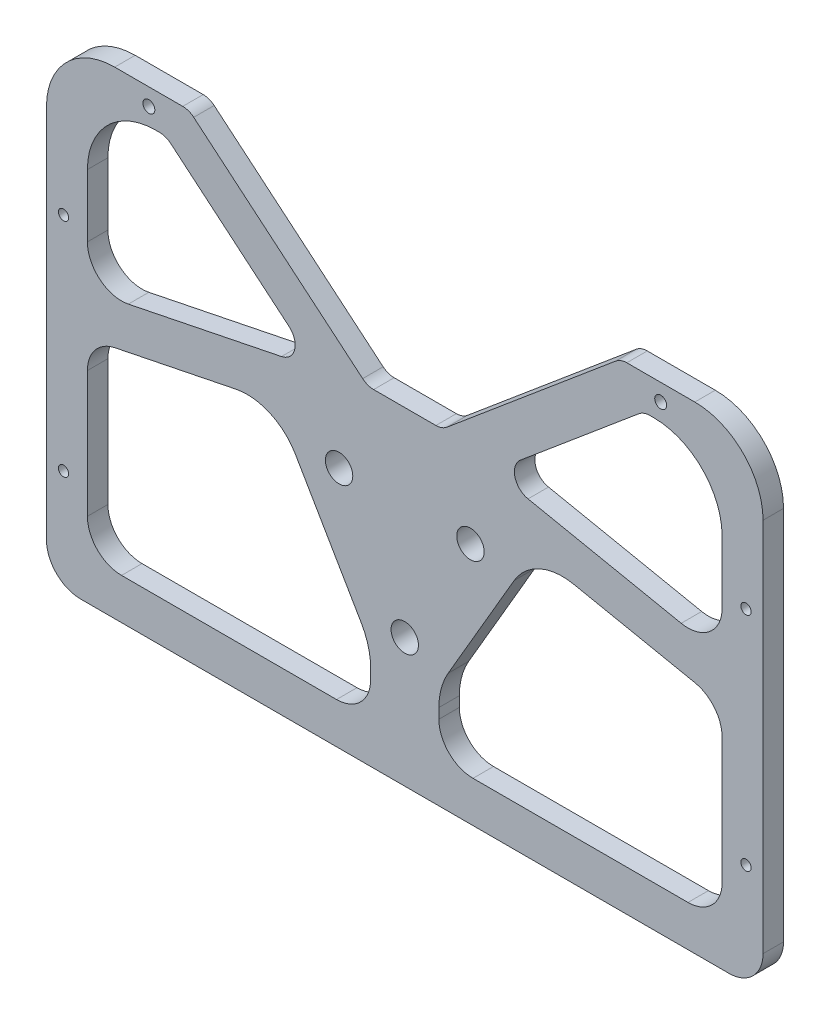
SolidWorks part; units mm, degrees
ref_plane "前基準面" through (0, 0, 0) normal (0, 0, 1) x (1, 0, 0)
ref_plane "上基準面" through (0, 0, 0) normal (0, 1, 0) x (1, 0, 0)
ref_plane "右基準面" through (0, 0, 0) normal (1, 0, 0) x (0, 0, -1)
sketch "Sketch1" plane through (0, 0, 0) normal (0, 0, 1) x (1, 0, 0)
  line L0 (0, 83.5398) -> (0, -125.3098) construction
  line L2 (-95, -60) -> (95, -60)
  line L3 (-105, -50) -> (-105, 60)
  line L5 (105, -50) -> (105, 60)
  line L6 (-105, -60) -> (105, 60) construction
  line L7 (-105, 60) -> (105, -60) construction
  line L8 (93, -1.0046) -> (93, -38)
  line L9 (-83, -48) -> (-20, -48)
  line L10 (-93, -38) -> (-93, -1.0046)
  line L11 (-93, 48) -> (93, 48) construction
  line L12 (93, -48) -> (93, 48) construction
  line L13 (-93, -48) -> (93, -48) construction
  line L14 (-93, -48) -> (-93, 48) construction
  line L15 (-105, 60) -> (105, 60) construction
  line L16 (-105, -60) -> (-105, 60) construction
  line L17 (-105, -60) -> (105, -60) construction
  line L18 (105, -60) -> (105, 60) construction
  line L19 (0, 0) -> (-61.5237, 35.5207) construction
  line L20 (84.9937, 8.7946) -> (49.4486, 16.0264)
  line L21 (-93, 31.651) -> (-93, 50)
  line L22 (-66.8269, 30) -> (70.1999, 30) construction
  line L23 (-84.9937, 8.7946) -> (-49.4486, 16.0264)
  line L24 (-32.0562, 8.2322) -> (-12.7184, -24.9642)
  line L25 (32.0562, 8.2322) -> (12.7184, -24.9642)
  line L26 (20, -48) -> (83, -48)
  line L27 (93, 31.651) -> (93, 50)
  line L28 (-10, -38) -> (-10, -35.0313)
  line L29 (-100, 73.1057) -> (-100, -98.0123) construction
  line L30 (10, -38) -> (10, -35.0313)
  line L31 (100, 71.0716) -> (100, -107.1657) construction
  line L32 (-81.0063, 21.8517) -> (-42.9297, 29.5985)
  line L33 (81.0063, 21.8517) -> (42.9297, 29.5985)
  line L34 (-38.9423, 30) -> (38.9423, 30)
  line L35 (-85, 80) -> (85, 80)
  line L37 (-73, 70) -> (73, 70)
  arc A0 (-105, 60) -> (-85, 80) centre (-85, 60) cw
  arc A1 (93, -38) -> (83, -48) centre (83, -38) cw
  arc A2 (-83, -48) -> (-93, -38) centre (-83, -38) cw
  arc A5 (-105, -50) -> (-95, -60) centre (-95, -50) ccw
  arc A6 (95, -60) -> (105, -50) centre (95, -50) ccw
  arc A7 (105, 60) -> (85, 80) centre (85, 60) ccw
  arc A12 (-12.7184, -24.9642) -> (-10, -35.0313) centre (-30, -35.0313) cw
  arc A13 (12.7184, -24.9642) -> (10, -35.0313) centre (30, -35.0313) ccw
  arc A14 (32.0562, 8.2322) -> (49.4486, 16.0264) centre (46.188, 0) cw
  arc A15 (-32.0562, 8.2322) -> (-49.4486, 16.0264) centre (-46.188, 0) ccw
  arc A17 (38.9423, 30) -> (42.9297, 29.5985) centre (38.9423, 10) cw
  arc A18 (-42.9297, 29.5985) -> (-38.9423, 30) centre (-38.9423, 10) cw
  arc A19 (20, -48) -> (10, -38) centre (20, -38) cw
  arc A20 (-20, -48) -> (-10, -38) centre (-20, -38) ccw
  arc A21 (-93, -1.0046) -> (-84.9937, 8.7946) centre (-83, -1.0046) cw
  arc A22 (93, -1.0046) -> (84.9937, 8.7946) centre (83, -1.0046) ccw
  arc A23 (93, 31.651) -> (81.0063, 21.8517) centre (83, 31.651) cw
  arc A24 (-93, 31.651) -> (-81.0063, 21.8517) centre (-83, 31.651) ccw
  arc A25 (93, 50) -> (73, 70) centre (73, 50) ccw
  arc A26 (-73, 70) -> (-93, 50) centre (-73, 50) ccw
  spline S1 degree 3 poles (-85.7038, 19.8656) (-85.7188, 19.8643) (-85.8694, 19.8508) (-86.1654, 19.8244) (-86.7586, 19.7722) (-87.5568, 19.705) (-88.5978, 19.6254) (-89.3837, 19.5729) (-90.1557, 19.5266) (-90.9081, 19.4857) (-91.7011, 19.452) (-92.5653, 19.4219) (-93.5061, 19.3971) (-94.6818, 19.3863) (-95.6597, 19.3925) (-96.4117, 19.4054) (-97.1825, 19.4275) (-97.8845, 19.4569) (-98.4218, 19.486) (-98.9655, 19.5197) (-99.61, 19.5665) (-100.317, 19.6301) (-100.8904, 19.6904) (-101.3238, 19.7407) (-101.76, 19.7964) (-102.1984, 19.8577) (-102.6385, 19.9251) (-102.9327, 19.9743) (-103.0799, 20) knots 0.184037 0.184037 0.184037 0.184037 0.1875 0.21875 0.25 0.3125 0.375 0.4375 0.444444 0.5 0.555556 0.5625 0.625 0.6875 0.71875 0.75 0.78125 0.8125 0.833333 0.84375 0.875 0.90625 0.921875 0.9375 0.953125 0.96875 0.984375 1 1 1 1 construction
  point P3 (0, 0)
  point P23 (-105, 80)
  point P40 (95, 22)
  point P47 (0, 0)
  point P50 (-34.641, 20)
  point P60 (-10, -29.6307)
  point P63 (10, -29.6307)
  point P66 (34.641, 20)
  point P69 (-34.641, 20)
  point P87 (40.9562, 30)
  point P90 (-40.9562, 30)
  point P100 (-93, 7.1657)
  point P103 (93, 7.1657)
  point P106 (93, 19.4116)
  point P109 (-93, 19.4116)
  dimension "D4" = 10
  dimension "D5" = 149.778
  dimension "D6" = 140
  dimension "D13" = 20
  dimension "D9" = 20
  dimension "D12" = 10
  dimension "D2" = 20
  dimension "D10" = 20
  dimension "D17" = 40
  dimension "D18" = 10
  dimension "D19" = 10
  dimension "D1" = 120
  dimension "D8" = 70
  dimension "D11" = 20
  dimension "D14" = 11.5
  dimension "D15" = 5
  dimension "D7" = 210
  dimension "D16" = 12
  dimension "D3" = 12
extrude "Boss-Extrude1" add sketch "Sketch1" along normal mid plane 6
sketch "Sketch2" plane through (0, 0, 3) normal (0, 0, 1) x (1, 0, 0)
  line L0 (100, 71.0716) -> (100, -107.1657) construction
  line L1 (-95, -60) -> (95, -60) construction
  line L4 (0, 83.5398) -> (0, -125.3098) construction
  circle A0 centre (100, 35) radius 1.5
  circle A1 centre (100, -30) radius 1.5
  circle A2 centre (-100, -30) radius 1.5
  circle A3 centre (-100, 35) radius 1.5
  dimension "D1" = 3
  dimension "D2" = 3
  dimension "D3" = 30
  dimension "D4" = 65
extrude "Cut-Extrude1" cut sketch "Sketch2" against normal through all both and the other way through all
sketch "Sketch3" plane through (0, 0, 3) normal (0, 0, 1) x (1, 0, 0)
  line L0 (0, 0) -> (-19.2474, 11.1125) construction
  line L1 (19.2474, 11.1125) -> (0, 0) construction
  line L2 (0, -22.225) -> (0, 0) construction
  circle A0 centre (0, 0) radius 22.225 construction
  dimension "D1" = 44.45
  dimension "D2" = 120
  dimension "D3" = 120
hole_wizard "O (0.316) Diameter Hole1" positions "Sketch4" profile "Sketch5" hole size "O" standard "ANSI Inch"
sketch "Sketch4" plane through (0, 0, 3) normal (0, 0, 1) x (1, 0, 0)
  point P0 (-19.2474, 11.1125)
  point P3 (19.2474, 11.1125)
  point P6 (0, -22.225)
sketch "Sketch5" plane through (-19.2474, 11.1125, 3) normal (1, 0, 0) x (0, -1, 0)
  line L0 (0, 0) -> (0, 12.4114)
  line L1 (0, 12.4114) -> (4.0132, 10)
  line L2 (4.0132, 10) -> (4.0132, 0)
  line L5 (4.0132, 0) -> (0, 0)
  line L10 (0, 12.4114) -> (-4.0132, 10) construction
  line L11 (0, -6.35) -> (0, 107.95) construction
  dimension "Hole Dia." = 8.0264
  dimension "Hole Depth" = 10
  dimension "Drill Angle" = 118
sketch "Sketch6" plane through (0, 0, 3) normal (0, 0, 1) x (1, 0, 0)
  line L0 (85, 80) -> (-85, 80) construction
  line L1 (-70, 80) -> (70, 80)
  line L2 (-70, 80) -> (-70, 70)
  line L3 (-70, 70) -> (70, 70)
  line L4 (70, 80) -> (70, 70)
  line L5 (73, 70) -> (-73, 70) construction
  circle A0 centre (0, 0) radius 22.225 construction
  dimension "D1" = 70
  dimension "D2" = 70
extrude "Cut-Extrude2" cut sketch "Sketch6" against normal blind 10
sketch "Sketch7" plane through (0, 0, 3) normal (0, 0, 1) x (1, 0, 0)
  circle A0 centre (-75, 75) radius 1.75
  circle A1 centre (75, 75) radius 1.75
  circle A2 centre (0, 0) radius 22.225 construction
  dimension "D1" = 3.5
  dimension "D2" = 3.5
  dimension "D3" = 75
  dimension "D4" = 75
  dimension "D5" = 75
extrude "Cut-Extrude3" cut sketch "Sketch7" against normal blind 10
sketch "Sketch8" plane through (0, 0, -3) normal (0, 0, -1) x (-1, 0, 0)
  line L0 (-70, 80) -> (-70, 70)
  line L1 (-70, 70) -> (-25.9648, 33.05)
  line L5 (69.8215, 80) -> (70, 80)
  line L6 (70, 80) -> (70, 70)
  line L7 (70, 70) -> (25.9648, 33.05)
  line L10 (-73, 70) -> (-70, 70) construction
  line L11 (70, 70) -> (73, 70) construction
  line L13 (-70, 80) -> (-63.2489, 80)
  line L14 (-63.2489, 80) -> (-10.9392, 36.107)
  line L15 (70, 80) -> (63.2489, 80)
  line L16 (63.2489, 80) -> (10.9392, 36.107)
  line L17 (-85, 80) -> (-70, 80) construction
  line L18 (10.9392, 36.107) -> (-10.9392, 36.107)
  line L21 (42.9297, 29.5985) -> (25.9648, 33.05)
  line L22 (-25.9648, 33.05) -> (-42.9297, 29.5985)
  line L24 (81.0063, 21.8517) -> (42.9297, 29.5985) construction
  line L27 (-42.9297, 29.5985) -> (-81.0063, 21.8517) construction
  line L28 (25.9648, 33.05) -> (10.9392, 36.107) construction
  line L29 (-10.9392, 36.107) -> (-25.9648, 33.05) construction
  line L30 (42.9297, 29.5985) -> (-42.9297, 29.5985)
  dimension "D1" = 140
  dimension "D2" = 140
  dimension "D3" = 12
  dimension "D4" = 12
extrude "Boss-Extrude3" add sketch "Sketch8" against normal blind 6 contours L6 L7 | L0 L1 region at (66.6244, 78.512, -3)
fillet "Fillet2" radius 5 8 edges at (-70, 70, 0) (70, 70, 0) (-63.2489, 80, 0) (63.2489, 80, 0) (10.9392, 36.107, 0) (-10.9392, 36.107, 0) (-25.9648, 33.05, 0) (25.9648, 33.05, 0)
